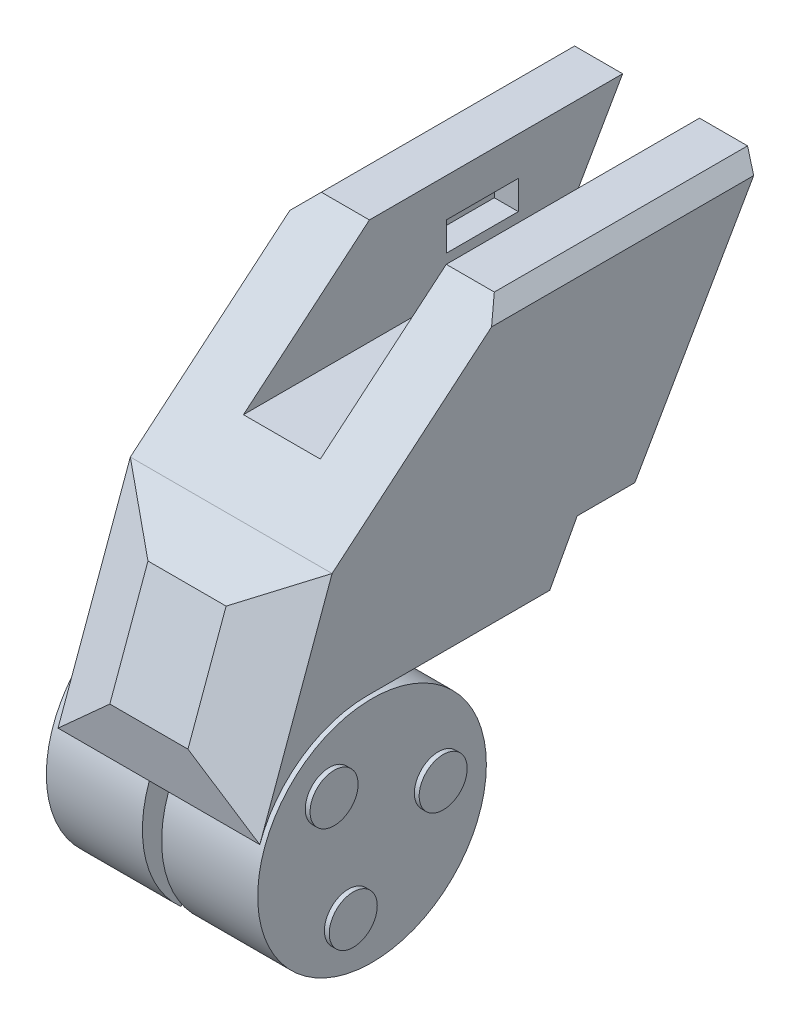
SolidWorks part; units mm, degrees
ref_plane "Front Plane" through (0, 0, 0) normal (0, 0, 1) x (1, 0, 0)
ref_plane "Top Plane" through (0, 0, 0) normal (0, 1, 0) x (1, 0, 0)
ref_plane "Right Plane" through (0, 0, 0) normal (1, 0, 0) x (0, 0, -1)
sketch "Sketch1" plane through (0, 0, 0) normal (1, 0, 0) x (0, 0, -1)
  circle A0 centre (0, 0) radius 11.9
  dimension "D1" = 23.8
extrude "Boss-Extrude1" add sketch "Sketch1" along normal blind 10 from offset 1
extrude "Boss-Extrude3" add sketch "Sketch1<3>" against normal blind 10 from offset 1 separate body offset against normal yes
sketch "Sketch1<3>" plane through (0, 0, 0) normal (1, 0, 0) x (0, 0, -1) same geometry as "Sketch1"
sketch "Sketch3" plane through (-1, 0, 0) normal (1, 0, 0) x (0, 0, -1)
  circle A0 centre (0, 0) radius 6
  dimension "D1" = 12
extrude "Cut-Extrude1" cut sketch "Sketch3" against normal blind 4
sketch "Sketch4" plane through (1, 0, 0) normal (-1, 0, 0) x (0, 0, 1)
  circle A0 centre (0, 0) radius 6
  dimension "D1" = 12
extrude "Cut-Extrude2" cut sketch "Sketch4" against normal blind 4
sketch "Sketch15" plane through (0, 0, 0) normal (1, 0, 0) x (0, 0, -1)
  line L0 (0, 0) -> (0, 11.9) construction
  line L1 (0, 0) -> (-11.1823, 4.07) construction
  line L2 (0, 11.9) -> (19, 11.9)
  line L3 (19, 11.9) -> (21.8569, 17.1762)
  line L4 (21.8569, 17.1762) -> (27.8569, 17.1762)
  line L5 (27.8569, 17.1762) -> (41.0844, 40.1702)
  line L6 (41.0844, 40.1702) -> (14.7272, 40.1702)
  line L7 (14.7272, 40.1702) -> (-3.6579, 24.7433)
  line L8 (-3.6579, 24.7433) -> (-11.1823, 4.07)
  circle A0 centre (0, 0) radius 11.9 construction
  arc A1 (-11.1823, 4.07) -> (0, 11.9) centre (0, 0) cw
  dimension "D1" = 70
  dimension "D2" = 19
  dimension "D3" = 6
  dimension "D4" = 6
  dimension "D5" = 22.994
  dimension "D6" = 60.09
  dimension "D7" = 22
  dimension "D8" = 30
  dimension "D9" = 24
extrude "Boss-Extrude9" add sketch "Sketch15" along normal mid plane 21
sketch "Sketch16" plane through (0, 4.07, 11.1823) normal (0, 0.342, 0.9397) x (1, 0, 0)
  line L6 (-10.5, 22) -> (-10.5, 0)
  line L7 (-10.5, 0) -> (-1, 0)
  line L8 (-1, 0) -> (1, 0)
  line L9 (1, 0) -> (10.5, 0)
  line L10 (10.5, 0) -> (10.5, 22)
  line L11 (10.5, 22) -> (-10.5, 22)
  line L12 (-10.5, 22) -> (-10.5, 0)
  line L13 (-10.5, 0) -> (-1, 0)
  line L14 (-1, 0) -> (1, 0)
  line L15 (1, 0) -> (10.5, 0)
  line L16 (10.5, 0) -> (10.5, 22)
  line L17 (10.5, 22) -> (-10.5, 22)
  dimension "D1" = 0
extrude "Boss-Extrude10" add sketch "Sketch16" along normal blind 3
chamfer "Chamfer4" distance 3 angle 60 2 edges at (0, 5.0961, 14.0014) (0, 25.7693, 6.477) first distance on face at (0, 4.4121, 12.122) first distance on face at (0, 25.2563, 5.0674)
chamfer "Chamfer5" distance 3 angle 65 2 edges at (-10.5, 15.4327, 10.2392) (10.5, 15.4327, 10.2392) first distance on face at (-10.5, 19.9934, -8.7972) first distance on face at (10.5, 19.9934, -8.7972)
sketch "Sketch17" plane through (11, 0, 0) normal (1, 0, 0) x (0, 0, -1)
  circle A0 centre (-4.4494, 5.404) radius 2.5
  circle A1 centre (6.9047, 1.1513) radius 2.5
  circle A2 centre (-2.4553, -6.5553) radius 2.5
  point P10 (0, 0)
  dimension "D2" = 5
  dimension "D1" = 7
  dimension "D3" = 5.404
  dimension "D4" = 3
extrude "Boss-Extrude11" add sketch "Sketch17" along normal blind 0.5
sketch "Sketch18" plane through (-11, 0, 0) normal (-1, 0, 0) x (0, 0, 1)
  circle A0 centre (4.4494, 5.404) radius 2.5
  circle A1 centre (-6.9047, 1.1513) radius 2.5
  circle A2 centre (2.4553, -6.5553) radius 2.5
extrude "Boss-Extrude12" add sketch "Sketch18" along normal blind 0.5
sketch "Sketch19" plane through (0, 0, 0) normal (0, 0, 1) x (1, 0, 0)
  line L0 (10.5, 40.1702) -> (-10.5, 40.1702) construction
  line L1 (-4, 40.1702) -> (4, 40.1702)
  line L2 (-4, 40.1702) -> (-4, 29.1702)
  line L3 (-4, 29.1702) -> (4, 29.1702)
  line L4 (4, 40.1702) -> (4, 29.1702)
  point P6 (0, 29.1702)
  dimension "D1" = 11
  dimension "D2" = 8
extrude "Cut-Extrude4" cut sketch "Sketch19" against normal through all
chamfer "Chamfer6" distance 1.5 angle 45 2 edges at (-10.5, 40.1702, -27.9058) (10.5, 40.1702, -27.9058)
scale "Scale1" bodies to scale 119 scale about origin uniform scaling yes scale factor 2
sketch "Sketch20" plane through (-8, 0, 0) normal (1, 0, 0) x (0, 0, -1)
  line L0 (69.5131, 58.3404) -> (3.2358, 58.3404) construction
  line L1 (45.4543, 72.3404) -> (60.4543, 72.3404)
  line L2 (45.4543, 72.3404) -> (45.4543, 66.3404)
  line L3 (45.4543, 66.3404) -> (60.4543, 66.3404)
  line L4 (60.4543, 72.3404) -> (60.4543, 66.3404)
  dimension "D1" = 16
  dimension "D2" = 15
  dimension "D3" = 6
  dimension "D4" = 8
extrude "Cut-Extrude5" cut sketch "Sketch20" against normal blind 5
mirror "Mirror4" about plane through (0, 0, 0) normal (1, 0, 0) of "Cut-Extrude5"
sketch "Sketch21" plane through (-2, 0, 0) normal (1, 0, 0) x (0, 0, -1)
  line L0 (4.8352, -10.9828) -> (9.5898, -21.7825)
  line L1 (-9.6252, -7.1662) -> (-15.7763, -17.8199)
  circle A0 centre (0, 0) radius 12 construction
  arc A1 (-9.6252, -7.1662) -> (4.8352, -10.9828) centre (0, 0) ccw
  arc A2 (0, 23.8) -> (-22.3647, 8.1401) centre (0, 0) ccw
  arc A3 (-22.3647, 8.1401) -> (0, 23.8) centre (0, 0) ccw
  arc A5 (-15.7763, -17.8199) -> (9.5898, -21.7825) centre (0, 0) ccw
  point P10 (5.025, -23.2635)
  point P11 (0, 0)
  point P12 (6.3114, -10.2062)
  point P13 (9.5898, -21.7825)
  dimension "D1" = 0
extrude "Cut-Extrude8" cut sketch "Sketch21" against normal blind 8 and the other way blind 12
